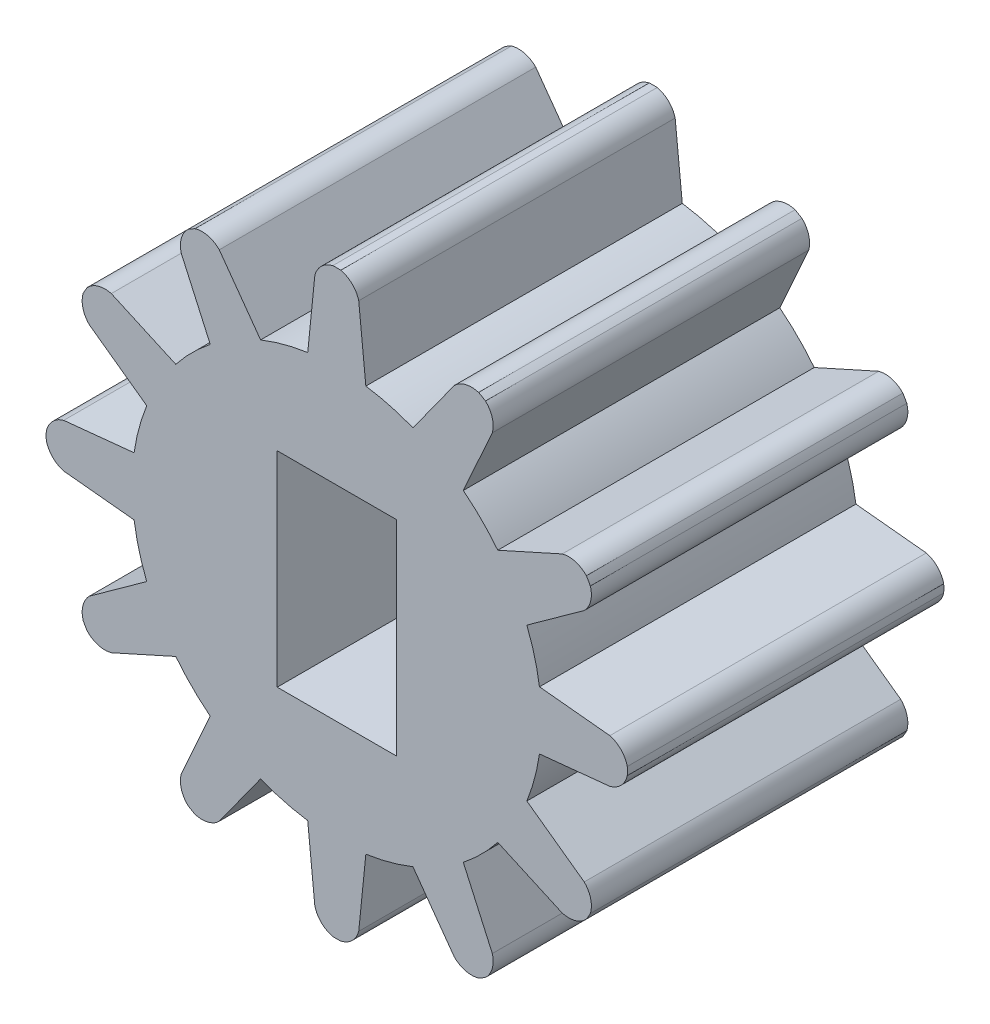
SolidWorks part; units mm, degrees
ref_plane "Front Plane" through (0, 0, 0) normal (0, 0, 1) x (1, 0, 0)
ref_plane "Top Plane" through (0, 0, 0) normal (0, 1, 0) x (1, 0, 0)
ref_plane "Right Plane" through (0, 0, 0) normal (1, 0, 0) x (0, 0, -1)
ref_plane "Plane1" through (0, 0, 20) normal (0, 0, 1) x (1, 0, 0)
ref_plane "Plane2" through (0, 0, 28.5) normal (0, 0, 1) x (1, 0, 0)
sketch "Sketch1" plane through (0, 0, 20) normal (0, 0, 1) x (1, 0, 0)
  circle A1 centre (0, 20.9252) radius 5.5
  dimension "D1" = 11
sketch "Sketch3" plane through (0, 0, 28.5) normal (0, 0, 1) x (1, 0, 0)
  line L0 (-3.9726, 20.9252) -> (15.3734, 20.9252) construction
  line L1 (0, 24.8978) -> (0, 8.7425) construction
  line L3 (-1.6, 23.6752) -> (1.6, 23.6752)
  line L4 (-1.6, 23.6752) -> (-1.6, 18.1752)
  line L5 (-1.6, 18.1752) -> (1.6, 18.1752)
  line L6 (1.6, 23.6752) -> (1.6, 18.1752)
  dimension "D1" = 3.2
  dimension "D2" = 5.5
  dimension "D3" = 1.6
  dimension "D4" = 2.75
extrude "Boss-Extrude2" add sketch "Sketch1" along normal blind 8.5
extrude "Cut-Extrude1" cut sketch "Sketch3" against normal blind 6
sketch "Sketch4" plane through (0, 0, 20) normal (0, 0, 1) x (1, 0, 0)
  line L0 (-0.5896, 28.2599) -> (-0.7807, 26.3695)
  line L1 (0, 28.7311) -> (0, 27.9031) construction
  line L2 (0.5896, 28.2599) -> (0.7807, 26.3695)
  line L3 (4.178, 26.9824) -> (3.3983, 25.2498)
  line L4 (3.1567, 27.5721) -> (2.046, 26.0305)
  line L5 (6.6468, 24.0819) -> (5.1053, 22.9713)
  line L6 (6.0572, 25.1032) -> (4.3246, 24.3235)
  line L7 (7.3347, 20.3356) -> (5.4443, 20.1445)
  line L8 (7.3347, 21.5149) -> (5.4443, 21.7059)
  line L9 (6.0572, 16.7473) -> (4.3246, 17.527)
  line L10 (6.6468, 17.7685) -> (5.1053, 18.8792)
  line L11 (3.1567, 14.2784) -> (2.046, 15.82)
  line L12 (4.178, 14.868) -> (3.3983, 16.6007)
  line L13 (-0.5896, 13.5906) -> (-0.7807, 15.4809)
  line L14 (0.5896, 13.5906) -> (0.7807, 15.4809)
  line L15 (-4.178, 14.868) -> (-3.3983, 16.6007)
  line L16 (-3.1567, 14.2784) -> (-2.046, 15.82)
  line L17 (-6.6468, 17.7685) -> (-5.1053, 18.8792)
  line L18 (-6.0572, 16.7473) -> (-4.3246, 17.527)
  line L19 (-7.3347, 21.5149) -> (-5.4443, 21.7059)
  line L20 (-7.3347, 20.3356) -> (-5.4443, 20.1445)
  line L21 (-6.0572, 25.1032) -> (-4.3246, 24.3235)
  line L22 (-6.6468, 24.0819) -> (-5.1053, 22.9713)
  line L23 (-3.1567, 27.5721) -> (-2.046, 26.0305)
  line L24 (-4.178, 26.9824) -> (-3.3983, 25.2498)
  circle A0 centre (0, 20.9252) radius 5.5 construction
  arc A1 (-0.5896, 28.2599) -> (-0.1067, 28.7283) centre (0.0391, 28.0948) cw
  arc A2 (-0.1067, 28.7283) -> (0.1067, 28.7283) centre (0, 26.7184) cw
  arc A3 (0.5896, 28.2599) -> (0.1067, 28.7283) centre (-0.0391, 28.0948) ccw
  arc A4 (-0.7807, 26.3695) -> (0.7807, 26.3695) centre (0, 20.9252) cw
  arc A5 (2.046, 26.0305) -> (3.3983, 25.2498) centre (0, 20.9252) cw
  arc A6 (4.178, 26.9824) -> (3.9939, 27.6295) centre (3.551, 27.1538) ccw
  arc A7 (3.8091, 27.7362) -> (3.9939, 27.6295) centre (2.8966, 25.9422) cw
  arc A8 (3.1567, 27.5721) -> (3.8091, 27.7362) centre (3.6186, 27.1147) cw
  arc A9 (4.3246, 24.3235) -> (5.1053, 22.9713) centre (0, 20.9252) cw
  arc A10 (6.6468, 24.0819) -> (6.811, 24.7344) centre (6.1895, 24.5438) ccw
  arc A11 (6.7043, 24.9191) -> (6.811, 24.7344) centre (5.017, 23.8218) cw
  arc A12 (6.0572, 25.1032) -> (6.7043, 24.9191) centre (6.2286, 24.4762) cw
  arc A13 (5.4443, 21.7059) -> (5.4443, 20.1445) centre (0, 20.9252) cw
  arc A14 (7.3347, 20.3356) -> (7.803, 20.8186) centre (7.1696, 20.9643) ccw
  arc A15 (7.803, 21.0319) -> (7.803, 20.8186) centre (5.7931, 20.9252) cw
  arc A16 (7.3347, 21.5149) -> (7.803, 21.0319) centre (7.1696, 20.8862) cw
  arc A17 (5.1053, 18.8792) -> (4.3246, 17.527) centre (0, 20.9252) cw
  arc A18 (6.0572, 16.7473) -> (6.7043, 16.9313) centre (6.2286, 17.3743) ccw
  arc A19 (6.811, 17.1161) -> (6.7043, 16.9313) centre (5.017, 18.0287) cw
  arc A20 (6.6468, 17.7685) -> (6.811, 17.1161) centre (6.1895, 17.3066) cw
  arc A21 (3.3983, 16.6007) -> (2.046, 15.82) centre (0, 20.9252) cw
  arc A22 (3.1567, 14.2784) -> (3.8091, 14.1143) centre (3.6186, 14.7357) ccw
  arc A23 (3.9939, 14.221) -> (3.8091, 14.1143) centre (2.8966, 15.9082) cw
  arc A24 (4.178, 14.868) -> (3.9939, 14.221) centre (3.551, 14.6967) cw
  arc A25 (0.7807, 15.4809) -> (-0.7807, 15.4809) centre (0, 20.9252) cw
  arc A26 (-0.5896, 13.5906) -> (-0.1067, 13.1222) centre (0.0391, 13.7557) ccw
  arc A27 (0.1067, 13.1222) -> (-0.1067, 13.1222) centre (0, 15.1321) cw
  arc A28 (0.5896, 13.5906) -> (0.1067, 13.1222) centre (-0.0391, 13.7557) cw
  arc A29 (-2.046, 15.82) -> (-3.3983, 16.6007) centre (0, 20.9252) cw
  arc A30 (-4.178, 14.868) -> (-3.9939, 14.221) centre (-3.551, 14.6967) ccw
  arc A31 (-3.8091, 14.1143) -> (-3.9939, 14.221) centre (-2.8966, 15.9082) cw
  arc A32 (-3.1567, 14.2784) -> (-3.8091, 14.1143) centre (-3.6186, 14.7357) cw
  arc A33 (-4.3246, 17.527) -> (-5.1053, 18.8792) centre (0, 20.9252) cw
  arc A34 (-6.6468, 17.7685) -> (-6.811, 17.1161) centre (-6.1895, 17.3066) ccw
  arc A35 (-6.7043, 16.9313) -> (-6.811, 17.1161) centre (-5.017, 18.0287) cw
  arc A36 (-6.0572, 16.7473) -> (-6.7043, 16.9313) centre (-6.2286, 17.3743) cw
  arc A37 (-5.4443, 20.1445) -> (-5.4443, 21.7059) centre (0, 20.9252) cw
  arc A38 (-7.3347, 21.5149) -> (-7.803, 21.0319) centre (-7.1696, 20.8862) ccw
  arc A39 (-7.803, 20.8186) -> (-7.803, 21.0319) centre (-5.7931, 20.9252) cw
  arc A40 (-7.3347, 20.3356) -> (-7.803, 20.8186) centre (-7.1696, 20.9643) cw
  arc A41 (-5.1053, 22.9713) -> (-4.3246, 24.3235) centre (0, 20.9252) cw
  arc A42 (-6.0572, 25.1032) -> (-6.7043, 24.9191) centre (-6.2286, 24.4762) ccw
  arc A43 (-6.811, 24.7344) -> (-6.7043, 24.9191) centre (-5.017, 23.8218) cw
  arc A44 (-6.6468, 24.0819) -> (-6.811, 24.7344) centre (-6.1895, 24.5438) cw
  arc A45 (-3.3983, 25.2498) -> (-2.046, 26.0305) centre (0, 20.9252) cw
  arc A46 (-3.1567, 27.5721) -> (-3.8091, 27.7362) centre (-3.6186, 27.1147) ccw
  arc A47 (-3.9939, 27.6295) -> (-3.8091, 27.7362) centre (-2.8966, 25.9422) cw
  arc A48 (-4.178, 26.9824) -> (-3.9939, 27.6295) centre (-3.551, 27.1538) cw
  circle A49 centre (0, 20.9252) radius 5.5 construction
  point P20 (0.1602, 28.7162)
  point P97 (0, 20.9252)
  point P98 (-0.3286, 28.1977)
  point P116 (0.77, 26.3711)
  dimension "D1" = 12
  dimension "D2" = 5.5
  dimension "D4" = 0.65
  dimension "D3" = 1.9
extrude "Boss-Extrude3" add sketch "Sketch4" along normal up to surface (8.5 mm away) up to face at (0, 20.9252, 28.5)
